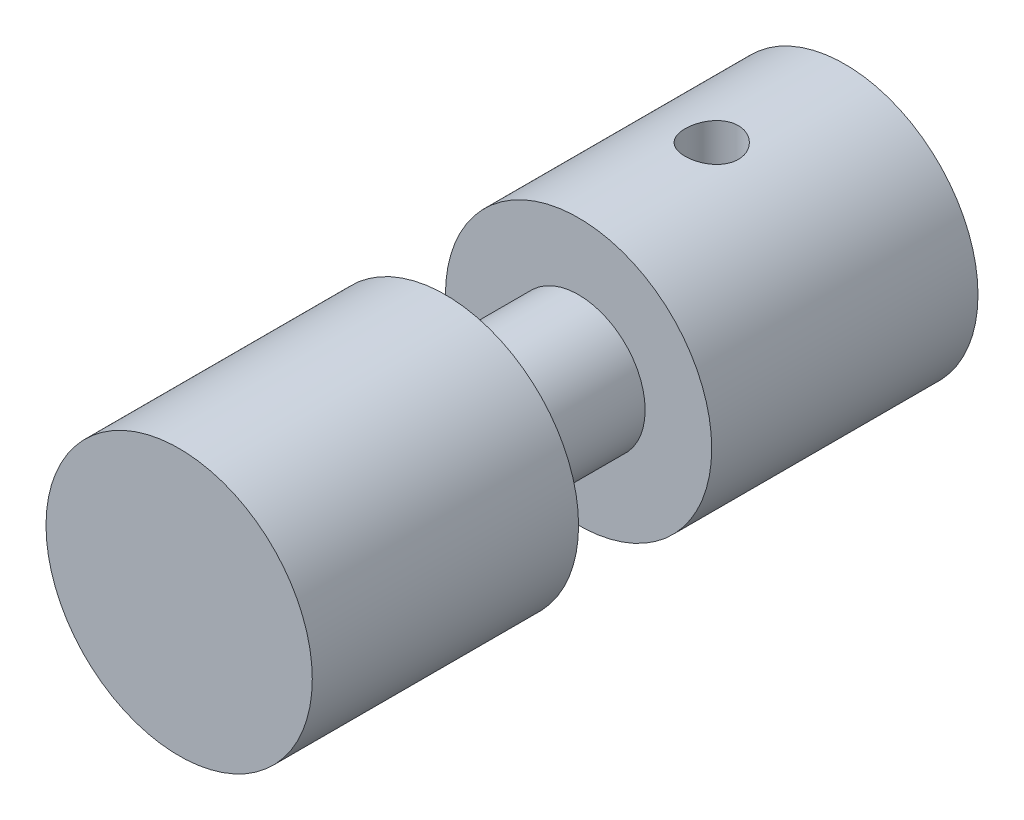
SolidWorks part; units mm, degrees
ref_plane "Plan de face" through (0, 0, 0) normal (0, 0, 1) x (1, 0, 0)
ref_plane "Plan de dessus" through (0, 0, 0) normal (0, 1, 0) x (1, 0, 0)
ref_plane "Plan de droite" through (0, 0, 0) normal (1, 0, 0) x (0, 0, -1)
sketch "Esquisse1" plane through (0, 0, 0) normal (0, 0, 1) x (1, 0, 0)
  circle A0 centre (0, 0) radius 5
  dimension "D1" = 10
extrude "Boss.-Extru.1" add sketch "Esquisse1" along normal blind 10
sketch "Esquisse2" plane through (0, 0, 10) normal (0, 0, 1) x (1, 0, 0)
  circle A0 centre (0, 0) radius 2.5
  dimension "D1" = 5
extrude "Boss.-Extru.2" add sketch "Esquisse2" along normal blind 5
sketch "Esquisse3" plane through (0, 0, 15) normal (0, 0, 1) x (1, 0, 0)
  circle A0 centre (0, 0) radius 5
extrude "Boss.-Extru.4" add sketch "Esquisse3" along normal blind 10
sketch "Esquisse4" plane through (0, 0, 0) normal (0, 0, -1) x (-1, 0, 0)
  circle A0 centre (0, 0) radius 1.5
  dimension "D1" = 3
extrude "Enlèv. mat.-Extru.1" cut sketch "Esquisse4" against normal blind 10
sketch "Esquisse5" plane through (0, 0, 0) normal (0, 1, 0) x (1, 0, 0)
  circle A0 centre (0, -5) radius 1
  dimension "D2" = 2
  dimension "D1" = 5
extrude "Enlèv. mat.-Extru.2" cut sketch "Esquisse5" along normal blind 10 and the other way blind 10
